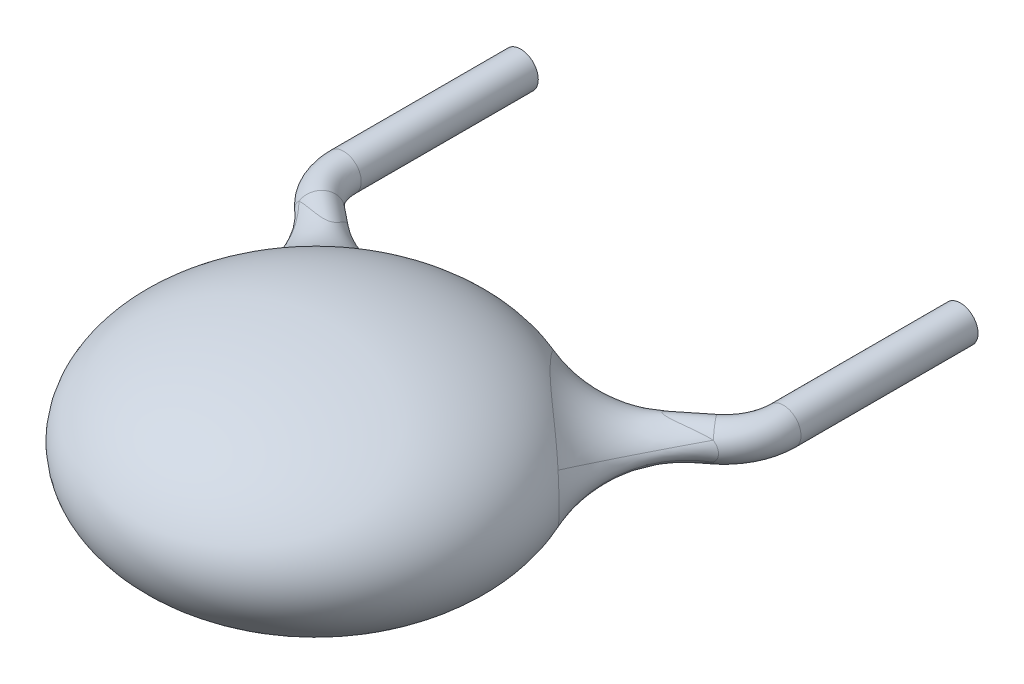
SolidWorks part; units mm, degrees
ref_plane "Front Plane" through (0, 0, 0) normal (0, 0, 1) x (1, 0, 0)
ref_plane "Top Plane" through (0, 0, 0) normal (0, 1, 0) x (1, 0, 0)
ref_plane "Right Plane" through (0, 0, 0) normal (1, 0, 0) x (0, 0, -1)
sketch "Sketch3" plane through (0, 0, 0) normal (1, 0, 0) x (0, 0, -1)
  line L7 (-5.25, 1.75) -> (-5.25, -1.75)
  ellipse E0 centre (-5.25, 0) end of major axis (-8.5, 0) minor radius 1.75 (-5.25, 1.75) -> (-5.25, -1.75) cw
  point P11 (-4.5, 0)
  dimension "D1" = 6.5
  dimension "D2" = 3.5
  dimension "D3" = 2
revolve "Revolve1" add sketch "Sketch3" angle 360 mid plane about L7
sketch "Sketch149" plane through (0, 0, 0) normal (0, 0, 1) x (1, 0, 0)
  line L0 (-3.75, 0) -> (3.75, 0) construction
  circle A0 centre (-3.75, 0) radius 0.3
  point P2 (0, 0)
  dimension "D3" = 0.6
  dimension "D1" = 7.5
sketch "Sketch150" plane through (0, 0, 0) normal (0, 1, 0) x (1, 0, 0)
  line L0 (-3.75, 2) -> (-3.75, -1.0194)
  line L2 (-3.3747, -1.8002) -> (0, -4.5)
  line L3 (0, -4.5) -> (3.3747, -1.8002)
  line L4 (3.75, -1.0194) -> (3.75, 2)
  arc A0 (3.3747, -1.8002) -> (3.75, -1.0194) centre (2.75, -1.0194) ccw
  arc A1 (-3.75, -1.0194) -> (-3.3747, -1.8002) centre (-2.75, -1.0194) ccw
  point P19 (3.75, -1.5)
  point P22 (-3.75, -1.5)
  dimension "D3" = 1
  dimension "D1" = 2
  dimension "D2" = 0.5
sweep "Sweep1" add profiles "Sketch149" path "Sketch150"
fillet "Fillet1" radius 2 2 edges at (1.8918, 0.0577, 2.6095) (-1.8918, -0.0577, 2.6095)
